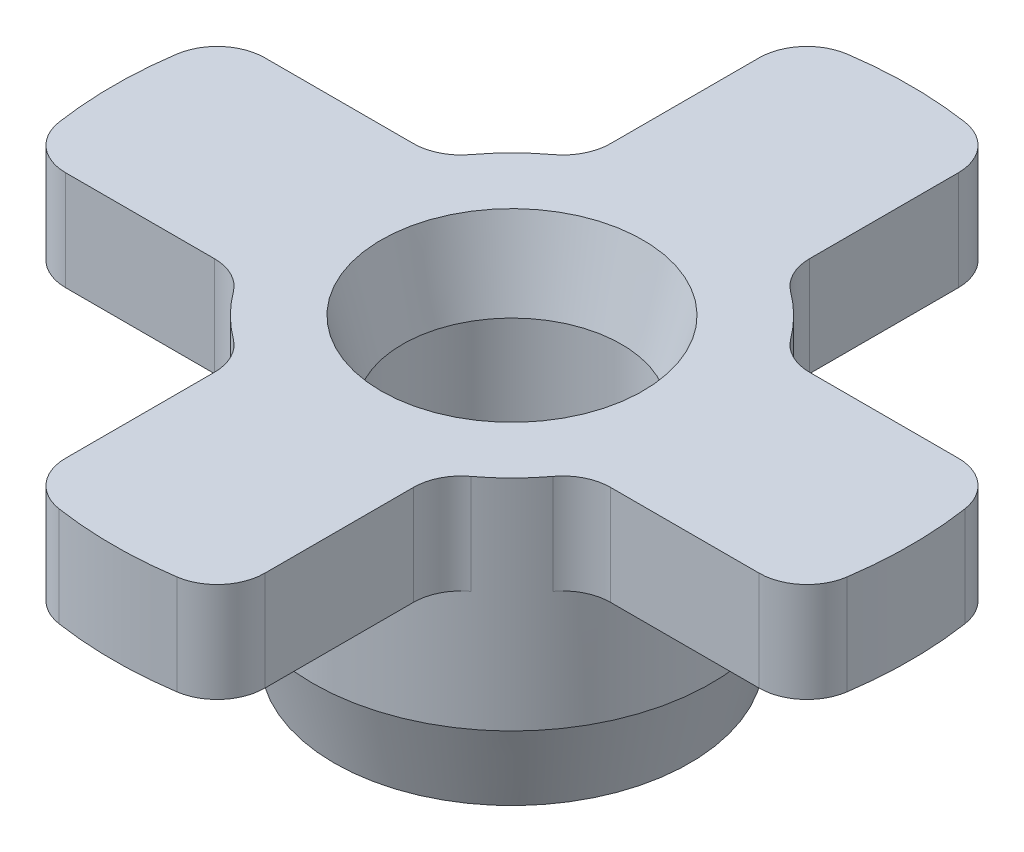
SolidWorks part; units mm, degrees
ref_plane "Front Plane" through (0, 0, 0) normal (0, 0, 1) x (1, 0, 0)
ref_plane "Top Plane" through (0, 0, 0) normal (0, 1, 0) x (1, 0, 0)
ref_plane "Right Plane" through (0, 0, 0) normal (1, 0, 0) x (0, 0, -1)
sketch "Sketch1" plane through (0, 0, 0) normal (0, 1, 0) x (1, 0, 0)
  line L0 (-3.175, 12.2967) -> (-3.175, 5.4993)
  line L1 (3.175, 12.2967) -> (3.175, 5.4993)
  line L2 (0, 0) -> (0, 12.7) construction
  line L3 (12.2967, 3.175) -> (5.4993, 3.175)
  line L4 (12.2967, -3.175) -> (5.4993, -3.175)
  line L5 (3.175, -12.2967) -> (3.175, -5.4993)
  line L6 (-3.175, -12.2967) -> (-3.175, -5.4993)
  line L7 (-12.2967, -3.175) -> (-5.4993, -3.175)
  line L8 (-12.2967, 3.175) -> (-5.4993, 3.175)
  circle A0 centre (0, 0) radius 6.35
  circle A1 centre (0, 0) radius 3.4925
  circle A2 centre (0, 0) radius 12.7
  point P25 (0, 0)
  dimension "D1" = 12.7
  dimension "D2" = 6.985
  dimension "D3" = 25.4
  dimension "D4" = 6.35
  dimension "D5" = 3.175
  dimension "D6" = 4
extrude "Boss-Extrude1" add sketch "Sketch1" along normal blind 3.175 contours L8 A2 L7 A0 | A0 L2 A2 L0 | L2 A0 L1 A2 | A1 A0 | L4 A2 L3 A0 | L6 A2 L5 A0 region at (-1.6053, 0, -9.3167) region at (-1.597, 0, -5.9601) region at (1.6053, 0, -9.3167) region at (-9.3167, 0, 0) region at (9.3167, 0, 0) region at (0, 0, 9.3167)
extrude "Boss-Extrude2" add sketch "Sketch1<3>" against normal blind 6.35 contours A1 A0 region at (0, 0, -6.1704)
sketch "Sketch1<3>" plane through (0, 0, 0) normal (0, 1, 0) x (1, 0, 0) same geometry as "Sketch1"
chamfer "Chamfer1" distance 2.54 angle 15 3 edges at (0, -6.35, 6.35) (0, -6.35, 3.4925) (0, 3.175, 3.4925) first distance on face at (0, 1.5875, 0) first distance on face at (0, 3.175, 3.4925)
fillet "Fillet2" radius 1.524 16 edges at (-3.175, 1.5875, -12.2967) (3.175, 1.5875, -12.2967) (3.175, 1.5875, -5.4993) (12.2967, 1.5875, -3.175) (12.2967, 1.5875, 3.175) (5.4993, 1.5875, 3.175) (5.4993, 1.5875, -3.175) (3.175, 1.5875, 5.4993) (3.175, 1.5875, 12.2967) (-3.175, 1.5875, 12.2967) (-3.175, 1.5875, 5.4993) (-5.4993, 1.5875, 3.175) (-12.2967, 1.5875, 3.175) (-12.2967, 1.5875, -3.175) (-5.4993, 1.5875, -3.175) (-3.175, 1.5875, -5.4993)
